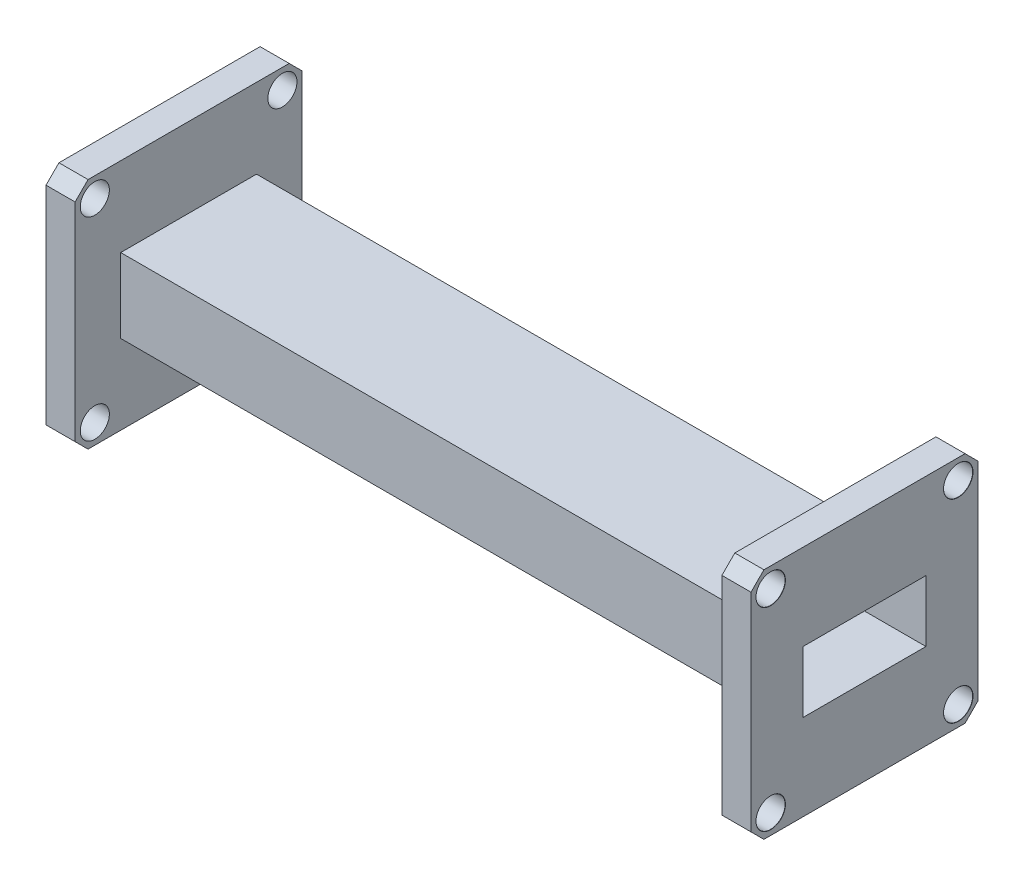
SolidWorks part; units mm, degrees
ref_plane "Спереди" through (0, 0, 0) normal (0, 0, 1) x (1, 0, 0)
ref_plane "Сверху" through (0, 0, 0) normal (0, 1, 0) x (1, 0, 0)
ref_plane "Справа" through (0, 0, 0) normal (1, 0, 0) x (0, 0, -1)
sketch "Эскиз1" plane through (0, 0, 0) normal (1, 0, 0) x (0, 0, -1)
  line L1 (-17.55, -18.05) -> (17.55, -18.05)
  line L2 (-17.55, -18.05) -> (-17.55, 18.05)
  line L3 (-17.55, 18.05) -> (17.55, 18.05)
  line L4 (17.55, -18.05) -> (17.55, 18.05)
  line L5 (-17.55, -18.05) -> (17.55, 18.05) construction
  line L6 (-17.55, 18.05) -> (17.55, -18.05) construction
  line L7 (-9.5, -4.75) -> (9.5, -4.75)
  line L8 (-9.5, -4.75) -> (-9.5, 4.75)
  line L9 (-9.5, 4.75) -> (9.5, 4.75)
  line L10 (9.5, -4.75) -> (9.5, 4.75)
  line L11 (-9.5, -4.75) -> (9.5, 4.75) construction
  line L12 (-9.5, 4.75) -> (9.5, -4.75) construction
  point P0 (0, 0)
  point P6 (0, 0)
  dimension "D1" = 35.1
  dimension "D2" = 36.1
  dimension "D3" = 9.5
  dimension "D4" = 19
extrude "Бобышка-Вытянуть1" add sketch "Эскиз1" along normal blind 4.5
sketch "Эскиз2" plane through (0, 0, 0) normal (-1, 0, 0) x (0, 0, 1)
  point P0 (12.5, 13)
  dimension "D1" = 12.5
  dimension "D2" = 13
ref_axis "Ось1" through (-53.9761, 0, 0) along (1, 0, 0)
chamfer "Фаска1" distance 2 4 edges at (2.25, -18.05, 17.55) (2.25, -18.05, -17.55) (2.25, 18.05, -17.55) (2.25, 18.05, 17.55)
sketch "Эскиз4" plane through (4.5, 0, 0) normal (1, 0, 0) x (0, 0, -1)
  line L1 (-9.5, -4.75) -> (9.5, -4.75)
  line L2 (-9.5, -4.75) -> (-9.5, 4.75)
  line L3 (-9.5, 4.75) -> (9.5, 4.75)
  line L4 (9.5, -4.75) -> (9.5, 4.75)
  line L5 (-9.5, -4.75) -> (9.5, 4.75) construction
  line L6 (-9.5, 4.75) -> (9.5, -4.75) construction
  line L7 (-10.5, -5.75) -> (10.5, -5.75)
  line L8 (-10.5, -5.75) -> (-10.5, 5.75)
  line L9 (-10.5, 5.75) -> (10.5, 5.75)
  line L10 (10.5, -5.75) -> (10.5, 5.75)
  line L11 (-10.5, -5.75) -> (10.5, 5.75) construction
  line L12 (-10.5, 5.75) -> (10.5, -5.75) construction
  point P0 (0, 0)
  point P7 (0, 0)
  dimension "D1" = 1
  dimension "D2" = 1
extrude "Бобышка-Вытянуть2" add sketch "Эскиз4" along normal blind 100
ref_plane "Плоскость4" through (104.5, 0, 0) normal (1, 0, 0) x (0, 0, -1)
sketch "Эскиз5" plane through (104.5, 0, 0) normal (1, 0, 0) x (0, 0, -1)
  line L1 (-17.55, -18.05) -> (17.55, -18.05)
  line L2 (-17.55, -18.05) -> (-17.55, 18.05)
  line L3 (-17.55, 18.05) -> (17.55, 18.05)
  line L4 (17.55, -18.05) -> (17.55, 18.05)
  line L5 (-17.55, -18.05) -> (17.55, 18.05) construction
  line L6 (-17.55, 18.05) -> (17.55, -18.05) construction
  line L7 (-9.5, -4.75) -> (9.5, -4.75)
  line L8 (-9.5, -4.75) -> (-9.5, 4.75)
  line L9 (-9.5, 4.75) -> (9.5, 4.75)
  line L10 (9.5, -4.75) -> (9.5, 4.75)
  line L11 (-9.5, -4.75) -> (9.5, 4.75) construction
  line L12 (-9.5, 4.75) -> (9.5, -4.75) construction
  point P0 (0, 0)
  point P6 (0, 0)
  dimension "D1" = 35.1
  dimension "D2" = 36.1
extrude "Бобышка-Вытянуть3" add sketch "Эскиз5" along normal blind 4.5
chamfer "Фаска2" distance 2 angle 45 4 edges at (106.75, -18.05, 17.55) (106.75, -18.05, -17.55) (106.75, 18.05, -17.55) (106.75, 18.05, 17.55)
sketch "Эскиз6" plane through (0, 0, 0) normal (-1, 0, 0) x (0, 0, 1)
  line L1 (-14.5, -15) -> (14.5, -15) construction
  line L2 (-14.5, -15) -> (-14.5, 15) construction
  line L3 (-14.5, 15) -> (14.5, 15) construction
  line L4 (14.5, -15) -> (14.5, 15) construction
  line L5 (-14.5, -15) -> (14.5, 15) construction
  line L6 (-14.5, 15) -> (14.5, -15) construction
  point P0 (0, 0)
  dimension "D1" = 29
  dimension "D2" = 30
hole_wizard "Отверстие с зазором M41" positions "Трехмерный эскиз1" profile "Эскиз7" hole size "M4" standard "ISO" end condition up to next
sketch3d "Трехмерный эскиз1"
  point P0 (0, 15, 14.5)
sketch "Эскиз7" plane through (0, 15, 14.5) normal (0, 1, 0) x (0, 0, 1)
  line L0 (0, 0) -> (0, 109)
  line L1 (0, 109) -> (2.25, 109)
  line L2 (2.25, 109) -> (2.25, 0.025)
  line L3 (2.25, 0.025) -> (2.275, 0)
  line L5 (2.275, 0) -> (0, 0)
  line L6 (-2.25, 0.025) -> (-2.275, 0) construction
  line L11 (0, -6.35) -> (0, 107.95) construction
  dimension "Диаметр сквозного отверстия" = 4.5
  dimension "Глубина сквозного отверстия" = 109
  dimension "Диаметр передней зенковки" = 4.55
  dimension "Угол передней зенковки" = 90
pattern_linear "Линейный массив1" count 2 spacing 29 along (0, 0, -1) count 2 spacing 30 along (0, -1, 0) of "Отверстие с зазором M41"
sketch "Эскиз8" plane through (109, 0, 0) normal (1, 0, 0) x (0, 0, -1)
  line L1 (-14.5, -15) -> (14.5, -15) construction
  line L2 (-14.5, -15) -> (-14.5, 15) construction
  line L3 (-14.5, 15) -> (14.5, 15) construction
  line L4 (14.5, -15) -> (14.5, 15) construction
  line L5 (-14.5, -15) -> (14.5, 15) construction
  line L6 (-14.5, 15) -> (14.5, -15) construction
  point P0 (0, 0)
  dimension "D1" = 29
  dimension "D2" = 30
hole_wizard "Отверстие с зазором M42" positions "Трехмерный эскиз2" profile "Эскиз9" hole size "M4" standard "ISO" end condition up to next
sketch3d "Трехмерный эскиз2"
  point P0 (109, 15, 14.5)
  point P3 (109, 15, -14.5)
  point P6 (109, -15, -14.5)
  point P9 (109, -15, 14.5)
sketch "Эскиз9" plane through (109, 15, 14.5) normal (0, 1, 0) x (0, 0, -1)
  line L0 (0, 0) -> (0, 4.5)
  line L1 (0, 4.5) -> (2.25, 4.5)
  line L2 (2.25, 4.5) -> (2.25, 0.025)
  line L3 (2.25, 0.025) -> (2.275, 0)
  line L5 (2.275, 0) -> (0, 0)
  line L6 (-2.25, 0.025) -> (-2.275, 0) construction
  line L11 (0, -6.35) -> (0, 107.95) construction
  dimension "Диаметр сквозного отверстия" = 4.5
  dimension "Глубина сквозного отверстия" = 4.5
  dimension "Диаметр передней зенковки" = 4.55
  dimension "Угол передней зенковки" = 90
